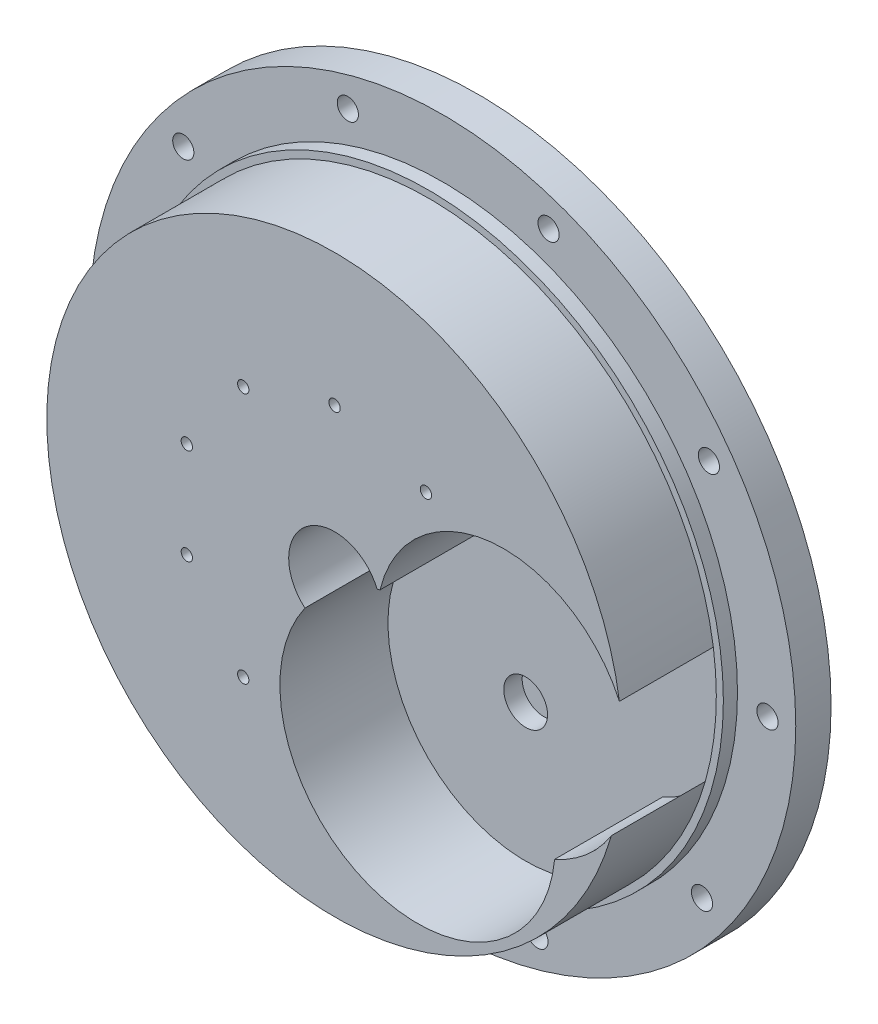
SolidWorks part; units mm, degrees
note: The reader was unsure of these and kept them because the rebuilt part matched: shared geometry of "草图1<10>", "草图1<8>", "草图1<9>".
ref_plane "前视基准面" through (0, 0, 0) normal (0, 0, 1) x (1, 0, 0)
ref_plane "上视基准面" through (0, 0, 0) normal (0, 1, 0) x (1, 0, 0)
ref_plane "右视基准面" through (0, 0, 0) normal (1, 0, 0) x (0, 0, -1)
other "Configuration Table"
sketch "草图1" plane through (0, 0, 0) normal (0, 0, 1) x (1, 0, 0)
  line L1 (25, -50) -> (-25, -50)
  line L2 (25, -50) -> (25, 50)
  line L3 (25, 50) -> (-25, 50)
  line L4 (-25, -50) -> (-25, 50)
  line L5 (25, -50) -> (-25, 50) construction
  line L6 (25, 50) -> (-25, -50) construction
  circle A5 centre (0, 0) radius 47.25
  circle A6 centre (0, 0) radius 50
  circle A7 centre (0, 0) radius 40.75
  circle A8 centre (0, 0) radius 41.75
  circle A9 centre (-13.425, 43.9974) radius 2.25
  circle A10 centre (-13.425, 43.9974) radius 1.5
  dimension "D1" = 94.5
  dimension "D2" = 100
  dimension "D3" = 81.5
  dimension "D4" = 83.5
  dimension "D7" = 3
  dimension "D8" = 4.5
  dimension "D5" = 50
  dimension "D6" = 100
extrude "凸台-拉伸1" add sketch "草图1" along normal blind 5 contours A6
extrude "凸台-拉伸2" add sketch "草图1<10>" along normal blind 2 from surface at 5 contours A8 | A7 starting at face at (50, 0, 5)
sketch "草图1<10>" plane through (0, 0, 0) normal (0, 0, 1) x (1, 0, 0) same geometry as "草图1"
extrude "切除-拉伸1" cut sketch "草图1<8>" along normal through all contours A10
sketch "草图1<8>" plane through (0, 0, 0) normal (0, 0, 1) x (1, 0, 0) same geometry as "草图1"
extrude "切除-拉伸2" cut sketch "草图1<9>" along normal blind 2 contours A9
sketch "草图1<9>" plane through (0, 0, 0) normal (0, 0, 1) x (1, 0, 0) same geometry as "草图1"
pattern_circular "阵列(圆周)1" count 10 over 360 about axis through (0, 0, 0) along (0, 0, 1) of "切除-拉伸1", "切除-拉伸2"
sketch "草图2" plane through (0, 0, 5) normal (0, 0, -1) x (-1, 0, 0)
  circle A0 centre (0, 0) radius 6.5
  circle A1 centre (-11.7557, -16.1803) radius 19.5
  circle A2 centre (-23.9462, -1.6066) radius 18
  circle A3 centre (0, 0) radius 30
  circle M19 centre (0, 0) radius 40.75
  dimension "D1" = 13
  dimension "D2" = 39
  dimension "D3" = 36
  dimension "D4" = 60
extrude "凸台-拉伸3" add sketch "草图2" against normal blind 15.3 from surface at 0 contours A3 A1 A0 A2 | A1 A3 A2 M19
sketch "草图3" plane through (0, 0, 20.3) normal (0, 0, 1) x (1, 0, 0)
  circle A0 centre (0, 22) radius 0.8
  dimension "D2" = 1.6
  dimension "D1" = 22
extrude "切除-拉伸3" cut sketch "草图3" against normal blind 4 contours A0
pattern_circular "阵列(圆周)2" count 10 over 360 about axis through (0, 0, 0) along (0, 0, 1) of "切除-拉伸3"
sketch "草图4" plane through (0, 0, 5) normal (0, 0, 1) x (1, 0, 0)
  circle A0 centre (11.7557, -16.1803) radius 3.1
  dimension "D1" = 6.2
extrude "切除-拉伸4" cut sketch "草图4" against normal blind 2.6
